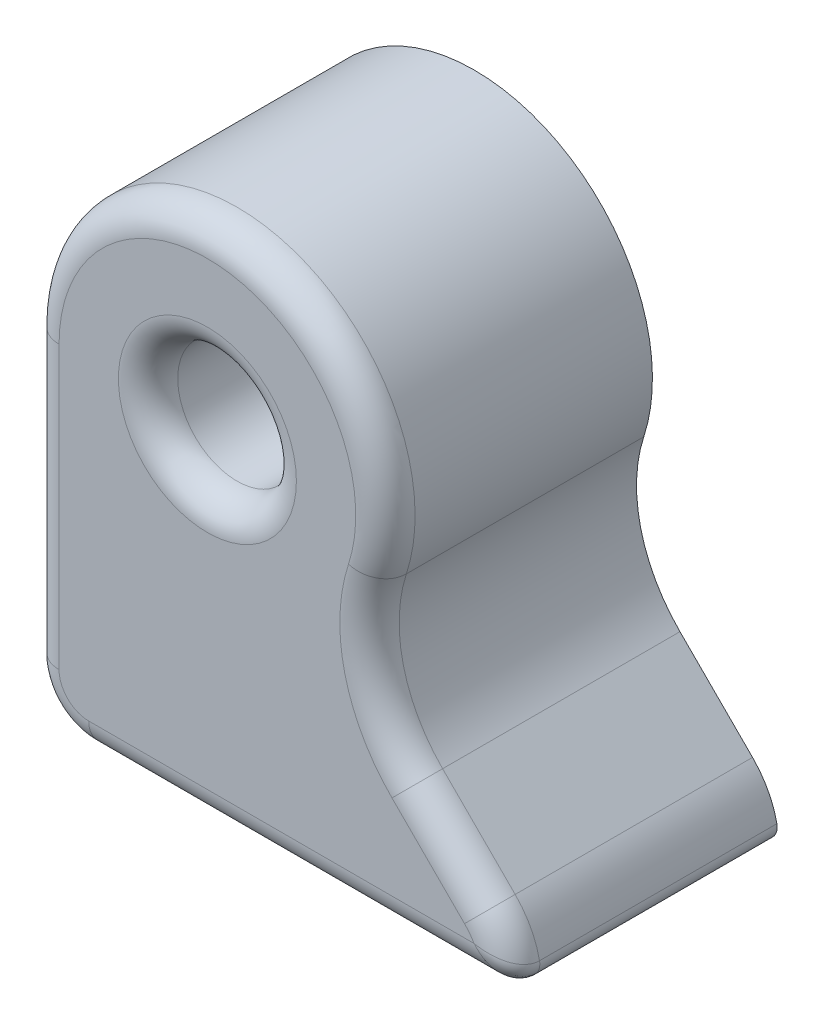
SolidWorks part; units mm, degrees
ref_plane "Front Plane" through (0, 0, 0) normal (0, 0, 1) x (1, 0, 0)
ref_plane "Top Plane" through (0, 0, 0) normal (0, 1, 0) x (1, 0, 0)
ref_plane "Right Plane" through (0, 0, 0) normal (1, 0, 0) x (0, 0, -1)
sketch "Sketch1" plane through (0, 0, 0) normal (0, 0, 1) x (1, 0, 0)
  line L0 (-47, 23) -> (-47, 0)
  line L1 (-47, 0) -> (-14.4903, 0)
  line L2 (-16.2513, 4.2513) -> (-26.5147, 14.5147)
  arc A0 (-26.5147, 14.5147) -> (-47, 23) centre (-35, 23) ccw
  arc A1 (-14.4903, 0) -> (-16.2513, 4.2513) centre (-20.5025, 0) ccw
  dimension "D1" = 24
  dimension "D2" = 45
extrude "Boss-Extrude1" add sketch "Sketch1" along normal blind 18
fillet "Fillet1" radius 10 1 edges at (-26.5147, 14.5147, 9)
fillet "Fillet2" radius 4 1 edges at (-47, 0, 9)
sketch "Sketch4" plane through (0, 0, 18) normal (0, 0, 1) x (1, 0, 0)
  circle A0 centre (-35, 23) radius 12
  dimension "D1" = 24
extrude "Cut-Extrude1" [suppressed] cut sketch "Sketch4" against normal blind 3
chamfer "Chamfer1" [suppressed] distance 3 angle 45
fillet "Fillet3" [suppressed] radius 1
fillet "Fillet4" [suppressed] radius 2
sketch "Sketch5" [suppressed] plane through (0, 0, 15) normal (0, 0, 1) x (1, 0, 0)
  circle A0 centre (-35, 23) radius 1.6
  dimension "D1" = 3.2
extrude "Cut-Extrude2" [suppressed] cut sketch "Sketch5" against normal through all
sketch "Sketch6" [suppressed] plane through (0, 0, 15) normal (0, 0, 1) x (1, 0, 0)
  circle A0 centre (-35, 23) radius 4
  dimension "D1" = 8
extrude "Cut-Extrude3" [suppressed] cut sketch "Sketch6" against normal offset from surface (11 mm away) 4 up to face at (-30.3059, 10.3428, 0)
sketch "Sketch7" [suppressed] plane through (0, 0, 0) normal (0, 0, -1) x (-1, 0, 0)
  circle A0 centre (35, 23) radius 10.4
  circle A1 centre (35, 23) radius 12
extrude "Boss-Extrude2" [suppressed] add sketch "Sketch7" against normal up to body separate body
fillet "Fillet5" radius 1 1 edges at (-14.4903, 0, 9)
fillet "Fillet6" radius 2 8 edges at (-18.6974, 6.6974, 18) (-15.2067, 2.8461, 18) (-14.8167, 0.3674, 18) (-29.2956, 0, 18) (-45.8284, 1.1716, 18) (-47, 13.5, 18) (-33.1265, 34.8528, 18) (-23.7955, 13.8772, 18)
sketch "Sketch8" plane through (0, 0, 18) normal (0, 0, 1) x (1, 0, 0)
  circle A0 centre (-35, 23) radius 1.6
  dimension "D1" = 3.2
extrude "Cut-Extrude4" cut sketch "Sketch8" against normal through all
sketch "Sketch9" plane through (0, 0, 18) normal (0, 0, 1) x (1, 0, 0)
  circle A0 centre (-35, 23) radius 4
  dimension "D1" = 8
extrude "Cut-Extrude5" cut sketch "Sketch9" against normal offset from surface (14 mm away) 4 up to face at (-33.4, 23, 0)
fillet "Fillet7" radius 2 1 edges at (-31, 23, 18)
